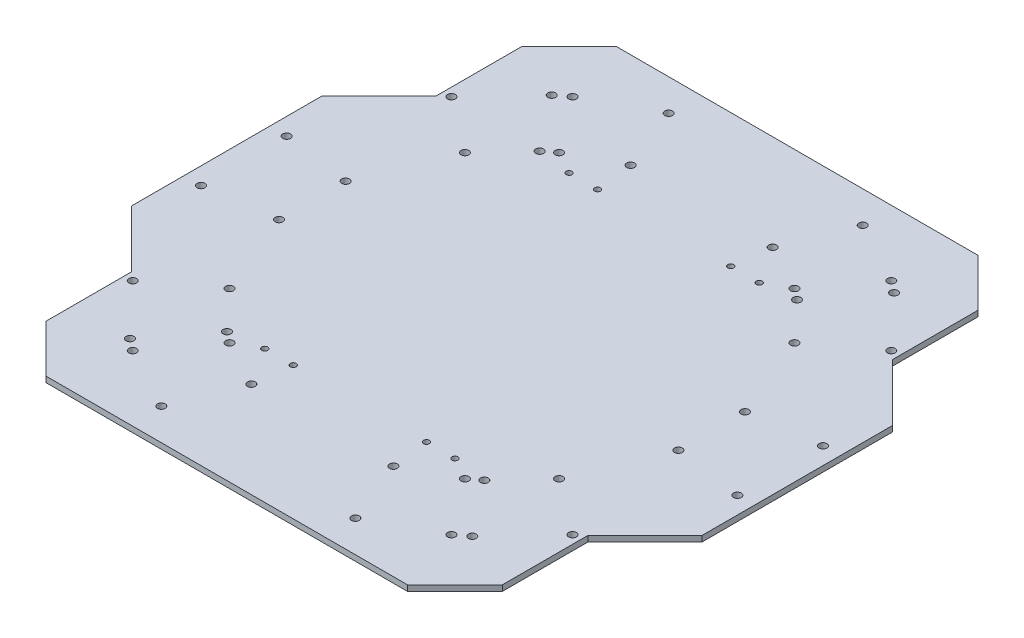
SolidWorks part; units mm, degrees
material "CF-ntbk"
ref_plane "Front Plane" through (0, 0, 0) normal (0, 0, 1) x (1, 0, 0)
ref_plane "Top Plane" through (0, 0, 0) normal (0, 1, 0) x (1, 0, 0)
ref_plane "Right Plane" through (0, 0, 0) normal (1, 0, 0) x (0, 0, -1)
sketch "Sketch1" plane through (0, 0, 0) normal (0, 1, 0) x (1, 0, 0)
  line L0 (-95, 150) -> (-120, 125)
  line L1 (-120, 125) -> (-120, 80)
  line L2 (-120, 80) -> (-150, 50)
  line L3 (-150, 50) -> (-150, -50)
  line L4 (-150, -50) -> (-120, -80)
  line L5 (-120, -80) -> (-120, -125)
  line L6 (-120, -125) -> (-95, -150)
  line L7 (-95, -150) -> (95, -150)
  line L8 (95, -150) -> (120, -125)
  line L9 (120, -125) -> (120, -80)
  line L10 (120, -80) -> (150, -50)
  line L11 (150, -50) -> (150, 50)
  line L12 (150, 50) -> (120, 80)
  line L13 (120, 80) -> (120, 125)
  line L14 (120, 125) -> (95, 150)
  line L15 (95, 150) -> (-95, 150)
  line L17 (-44.2539, 0) -> (44.2539, 0) construction
  line L18 (0, -44.7868) -> (0, 44.7868) construction
  dimension "D2" = 150
  dimension "D1" = 95
  dimension "D3" = 300
  dimension "D4" = 190
  dimension "D5" = 100
  dimension "D6" = 30
  dimension "D7" = 45
  dimension "D8" = 135
extrude "Boss-Extrude1" add sketch "Sketch1" along normal blind 3
sketch "Sketch2" plane through (0, 3, 0) normal (0, 1, 0) x (1, 0, 0)
  line L0 (-79.7985, -138.215) -> (79.7985, 138.215) construction
  line L1 (27.6134, 105.301) -> (76.8653, 76.8653) construction
  line L2 (-69.8318, 120.9522) -> (69.8318, -120.9522) construction
  line L3 (0, -44.7868) -> (0, 44.7868) construction
  line L5 (-44.2539, 0) -> (44.2539, 0) construction
  line L6 (-150.8166, 0) -> (150.8166, 0) construction
  line L7 (-118.217, -118.217) -> (118.217, 118.217) construction
  line L8 (-102.6144, 102.6144) -> (102.6144, -102.6144) construction
  line L9 (105, 17.5) -> (105, -25.4677) construction
  line L11 (30.9172, -103.3935) -> (75.1288, -77.8679) construction
  circle A0 centre (51.0144, 133.3596) radius 2.05
  circle A1 centre (37.3446, 99.6827) radius 2.05
  circle A2 centre (37.3446, -99.6827) radius 2.05
  circle A3 centre (51.0144, -133.3596) radius 2.05
  circle A4 centre (105, 17.5) radius 2.05
  circle A5 centre (141, 22.5) radius 2.05
  circle A12 centre (105, -17.5) radius 2.05
  circle A13 centre (141, -22.5) radius 2.05
  circle A16 centre (89.9856, -110.8596) radius 2.05
  circle A17 centre (67.6554, -82.1827) radius 2.05
  circle A18 centre (89.9856, 110.8596) radius 2.05
  circle A19 centre (67.6554, 82.1827) radius 2.05
  dimension "D1" = 4.1
  dimension "D3" = 30
  dimension "D5" = 30
  dimension "D10" = 45
  dimension "D11" = 45
  dimension "D4" = 17.5
  dimension "D7" = 105
  dimension "D15" = 105
  dimension "D17" = 105
  dimension "D20" = 17.5
  dimension "D24" = 17.5
  dimension "D29" = 17.5
  dimension "D12" = 17.5
  dimension "D16" = 17.5
  dimension "D9" = 22.5
  dimension "D22" = 22.5
  dimension "D23" = 36
  dimension "D26" = 36
  dimension "D8" = 22.5
  dimension "D13" = 22.5
  dimension "D14" = 36
  dimension "D21" = 36
  dimension "D6" = 22.5
  dimension "D18" = 22.5
  dimension "D19" = 36
  dimension "D25" = 36
extrude "HexCut1" cut sketch "Sketch2" against normal up to surface (3 mm away) up to face at (0, 0, 0)
mirror "HexCut2" about plane through (0, 0, 0) normal (1, 0, 0) of "HexCut1"
sketch "ConstructLines" plane through (0, 3, 0) normal (0, 1, 0) x (1, 0, 0)
  line L0 (0, 121.6855) -> (0, -121.6855) construction
  line L1 (-91.1915, 0) -> (91.1915, 0) construction
  line L2 (-44.2539, 0) -> (44.2539, 0) construction
ref_point "Point1"
sketch "Sketch5" plane through (0, 3, 0) normal (0, 1, 0) x (1, 0, 0)
  line L0 (0, 121.6855) -> (0, -121.6855) construction
  line L1 (-91.1915, 0) -> (91.1915, 0) construction
  circle A0 centre (35, 80) radius 1.55
  circle A1 centre (50, 80) radius 1.55
  dimension "D1" = 3.1
  dimension "D2" = 15
  dimension "D3" = 35
  dimension "D4" = 80
extrude "Cut-Extrude2" cut sketch "Sketch5" against normal up to surface (3 mm away) up to face at (-51.0144, 0, -131.3096)
pattern_linear "LPattern1" count 2 spacing 160 along (0, 0, 1) count 2 spacing 85 along (-1, 0, 0) of "Cut-Extrude2"
sketch "Sketch6" plane through (0, 3, 0) normal (0, 1, 0) x (1, 0, 0)
  line L0 (-103.0997, -103.0997) -> (103.0997, 103.0997) construction
  line L1 (0, 121.6855) -> (0, -121.6855) construction
  line L2 (69.8057, 78.6867) -> (81.2763, 67.2162) construction
  line L3 (-98.3117, 98.3117) -> (98.3117, -98.3117) construction
  line L4 (83.4139, -65.0786) -> (62.2362, -86.2562) construction
  circle A0 centre (86.6206, 61.8718) radius 2.05
  circle A1 centre (115.612, 83.7922) radius 2.05
  circle A2 centre (83.7922, 115.612) radius 2.05
  circle A3 centre (61.8718, 86.6206) radius 2.05
  circle A4 centre (86.6206, -61.8718) radius 2.05
  circle A5 centre (61.8718, -86.6206) radius 2.05
  circle A6 centre (83.7922, -115.612) radius 2.05
  circle A7 centre (115.612, -83.7922) radius 2.05
  dimension "D13" = 22.5
  dimension "D14" = 36
  dimension "D6" = 22.5
  dimension "D4" = 4.1
  dimension "D1" = 45
  dimension "D2" = 105
  dimension "D5" = 17.5
  dimension "D7" = 17.5
  dimension "D10" = 105
  dimension "D11" = 17.5
  dimension "D15" = 17.5
  dimension "D17" = 45
  dimension "D3" = 22.5
  dimension "D8" = 36
  dimension "D9" = 36
  dimension "D12" = 22.5
  dimension "D16" = 36
extrude "QuadCut1" cut sketch "Sketch6" against normal up to surface (3 mm away) up to face at (50, 0, 81.55)
mirror "QuadCut2" about plane through (0, 0, 0) normal (1, 0, 0) of "QuadCut1"
equation "\"ClampHoleDist\"= 36"
equation "\"ClampDistMid\"=105"
equation "\"Length\"= 300"
equation "\"D3@Sketch1\"=\"Length\""
equation "\"Width\"= 190"
equation "\"D1@Sketch1\"=\"Width\"/2"
equation "\"D2@Sketch1\"=\"Length\"/2"
equation "\"D4@Sketch1\"=\"Width\""
equation "\"D7@Sketch1\"=(\"Length\"- 210)/2"
equation "\"HoleZDist\"=80"
equation "\"D4@Sketch5\"=\"HoleZDist\""
equation "\"HoleXDist\"=35"
equation "\"D3@Sketch5\"=\"HoleXDist\""
equation "\"HoleSpacing\"=15"
equation "\"D2@Sketch5\"=\"HoleSpacing\""
equation "\"D3@LPattern1\"=\"HoleZDist\"*2"
equation "\"D4@LPattern1\"=\"HoleXDist\"*2+(\"HoleSpacing\")"
equation "\"ClampHoriDist\"=17.5"
equation "\"D4@Sketch2\"=\"ClampHoriDist\""
equation "\"D7@Sketch2\"=\"ClampDistMid\""
equation "\"D15@Sketch2\"=\"ClampDistMid\""
equation "\"D17@Sketch2\"=\"ClampDistMid\""
equation "\"D20@Sketch2\"=\"ClampHoriDist\""
equation "\"D24@Sketch2\"=\"ClampHoriDist\""
equation "\"D29@Sketch2\"=\"ClampHoriDist\""
equation "\"D12@Sketch2\"=\"ClampHoriDist\""
equation "\"ClampHoleSize\"=4.1"
equation "\"D1@Sketch2\"=\"ClampHoleSize\""
equation "\"D16@Sketch2\"=\"ClampHoriDist\""
equation "\"D2@Sketch6\"=\"ClampDistMid\""
equation "\"D4@Sketch6\"=\"ClampHoleSize\""
equation "\"D5@Sketch6\"=\"ClampHoriDist\""
equation "\"D7@Sketch6\"=\"ClampHoriDist\""
equation "\"D10@Sketch6\"=\"ClampDistMid\""
equation "\"D11@Sketch6\"=\"ClampHoriDist\""
equation "\"D15@Sketch6\"=\"ClampHoriDist\""
equation "\"FrontClampHoriDist\"=22.5"
equation "\"D9@Sketch2\"=\"FrontClampHoriDist\""
equation "\"D22@Sketch2\"=\"FrontClampHoriDist\""
equation "\"D23@Sketch2\"=\"ClampHoleDist\""
equation "\"D26@Sketch2\"=\"ClampHoleDist\""
equation "\"D8@Sketch2\"=\"FrontClampHoriDist\""
equation "\"D13@Sketch2\"=\"FrontClampHoriDist\""
equation "\"D14@Sketch2\"=\"ClampHoleDist\""
equation "\"D21@Sketch2\"=\"ClampHoleDist\""
equation "\"D6@Sketch2\"=\"FrontClampHoriDist\""
equation "\"D18@Sketch2\"=\"FrontClampHoriDist\""
equation "\"D19@Sketch2\"=\"ClampHoleDist\""
equation "\"D25@Sketch2\"=\"ClampHoleDist\""
equation "\"D3@Sketch6\"=\"FrontClampHoriDist\""
equation "\"D6@Sketch6\"=\"FrontClampHoriDist\""
equation "\"D8@Sketch6\"=\"ClampHoleDist\""
equation "\"D9@Sketch6\"=\"ClampHoleDist\""
equation "\"D12@Sketch6\"=\"FrontClampHoriDist\""
equation "\"D13@Sketch6\"=\"FrontClampHoriDist\""
equation "\"D14@Sketch6\"=\"ClampHoleDist\""
equation "\"D16@Sketch6\"=\"ClampHoleDist\""
